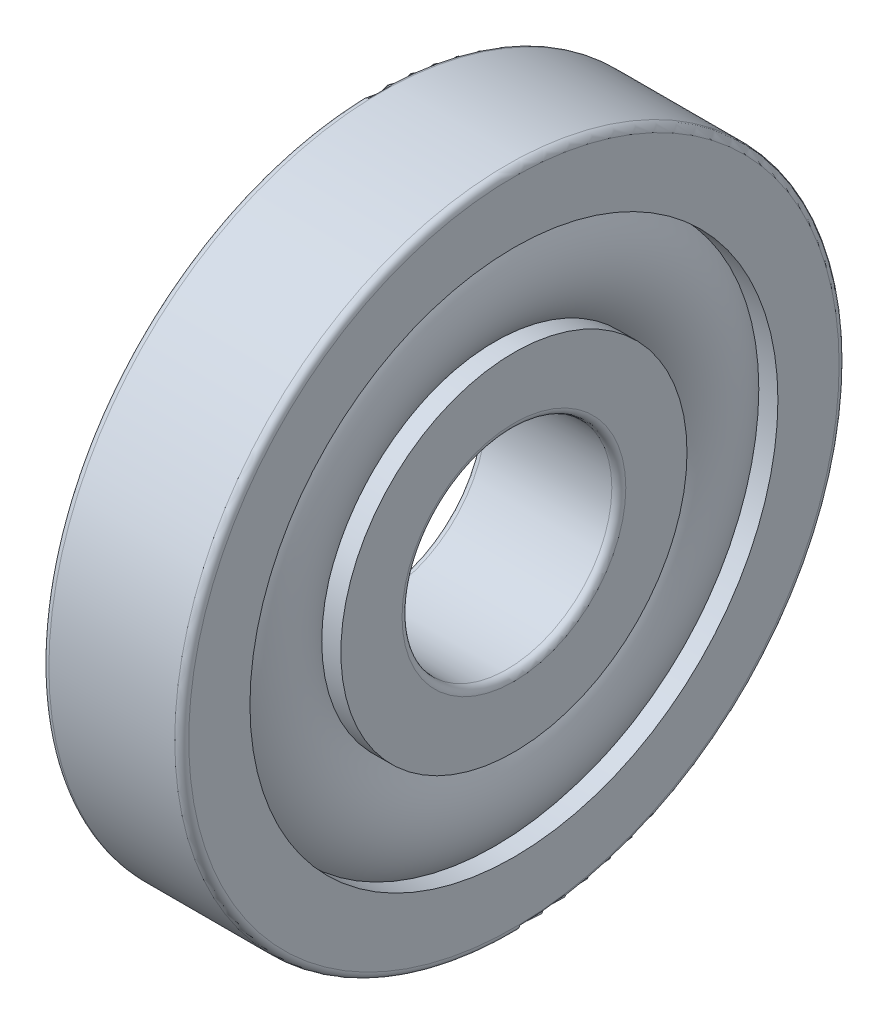
SolidWorks part; units mm, degrees
ref_plane "Plane1" through (0, 0, 0) normal (0, 0, 1) x (1, 0, 0)
ref_plane "Plane2" through (0, 0, 0) normal (0, 1, 0) x (1, 0, 0)
ref_plane "Plane3" through (0, 0, 0) normal (1, 0, 0) x (0, 0, -1)
sketch "Clipboard" plane through (0, 0, 0) normal (0, 0, 1) x (1, 0, 0)
  line L0 (-10, 0) -> (10, 0) construction
  line L1 (0, 0) -> (22.3471, -0.7804)
  line L2 (0, 0) -> (6.2462, 0.2181)
  line L3 (0, 0) -> (22.3471, -0.7804)
  line L4 (0, 0) -> (-22.3573, -0.3902)
  dimension "BallCLRad" = 6.25
sketch "CagSpiSke" plane through (0, 0, 0) normal (0, 0, 1) x (1, 0, 0)
  line L0 (0.195, 5.925) -> (0.195, 6.575)
  line L1 (0.195, 6.575) -> (-0.195, 6.575)
  line L2 (-0.195, 6.575) -> (-0.195, 5.925)
  line L3 (-0.195, 5.925) -> (0.195, 5.925)
  line L4 (-20.6375, 0) -> (20.6375, 0) construction
  line L5 (0, 0) -> (0, 23.7692) construction
  dimension "OD" = 13.15
  dimension "ID" = 11.85
revolve "CageSpine" add sketch "CagSpiSke" angle 0.001 about L4 reverse direction yes
ref_axis "Axis1" through (-50, 0, 0) along (1, 0, 0)
sketch "CagBalSke" plane through (0, 0, 0) normal (0, 0, 1) x (1, 0, 0)
  line L0 (-2.145, 6.25) -> (2.145, 6.25)
  line L1 (-1.905, 6.25) -> (1.905, 6.25) construction
  line L2 (-10, 0) -> (10, 0) construction
  line L3 (0, 0) -> (0, 24) construction
  arc A0 (2.145, 6.25) -> (-2.145, 6.25) centre (0, 6.25) cw
  dimension "BallCLRad" = 6.25
revolve "CageBall" [suppressed] add sketch "CagBalSke" angle 360 about L1 reverse direction yes
pattern_circular "CageBalls" [suppressed] count 2 every 180 about axis through (-50, 0, 0) along (1, 0, 0)
sketch "CagTrmODSke" plane through (0, 0, 0) normal (0, 0, 1) x (1, 0, 0)
  line L0 (2.146, 6.575) -> (2.146, 8.396)
  line L1 (2.146, 8.396) -> (-2.146, 8.396)
  line L2 (-2.146, 8.396) -> (-2.146, 6.575)
  line L3 (-2.146, 6.575) -> (2.146, 6.575)
  line L4 (-20.6375, 0) -> (20.6375, 0) construction
  line L5 (0, 0) -> (0, 25) construction
  dimension "Width" = 4.292
  dimension "ID" = 13.15
  dimension "OD" = 16.792
revolve "CageTrimOD" [suppressed] cut sketch "CagTrmODSke" angle 360 about L4 reverse direction yes
sketch "CagTrmIDSke" plane through (0, 0, 0) normal (0, 0, 1) x (1, 0, 0)
  line L0 (2.146, 4.106) -> (2.146, 5.925)
  line L1 (2.146, 5.925) -> (-2.146, 5.925)
  line L2 (-2.146, 5.925) -> (-2.146, 4.106)
  line L3 (-2.146, 4.106) -> (2.146, 4.106)
  line L4 (-20.6375, 0) -> (20.6375, 0) construction
  line L5 (0, 0) -> (0, 25) construction
  dimension "Width" = 4.292
  dimension "ID" = 8.212
  dimension "OD" = 11.85
revolve "CageTrimID" [suppressed] cut sketch "CagTrmIDSke" angle 360 about L4 reverse direction yes
sketch "BalSimSke" plane through (0, 0, 0) normal (0, 0, 1) x (1, 0, 0)
  line L0 (-10, 0) -> (10, 0) construction
  line L1 (-10, 6.25) -> (10, 6.25) construction
  line L2 (0, 0) -> (0, 23) construction
  circle A0 centre (0, 6.25) radius 1.95
  dimension "BallCLRad" = 6.25
  dimension "Ball_diameter" = 3.9
revolve "BallsSimplified" add sketch "BalSimSke" angle 360 about L0
sketch "BalDetSke" plane through (0, 0, 0) normal (0, 0, 1) x (1, 0, 0)
  line L0 (-1.95, 6.25) -> (1.95, 6.25)
  line L1 (-1.905, 6.25) -> (1.905, 6.25) construction
  line L2 (0, 0) -> (0, 25) construction
  arc A0 (1.95, 6.25) -> (-1.95, 6.25) centre (0, 6.25) cw
  dimension "BallCLRad" = 6.25
  dimension "Ball_diameter" = 3.9
revolve "BallDetailed" [suppressed] add sketch "BalDetSke" angle 360 about L1 reverse direction yes
sketch "InnRacSke" plane through (0, 0, 0) normal (0, 0, 1) x (1, 0, 0)
  line L0 (-1.4197, 4.95) -> (-2, 4.95)
  line L1 (-2, 4.95) -> (-2, 3.2)
  line L2 (-1.8, 3) -> (1.8, 3)
  line L3 (2, 3.2) -> (2, 4.95)
  line L4 (2, 4.95) -> (1.4197, 4.95)
  line L5 (-20.6375, 0) -> (20.6375, 0) construction
  line L6 (0, 0) -> (0, 30) construction
  arc A0 (-2, 3.2) -> (-1.8, 3) centre (-1.8, 3.2) ccw
  arc A1 (1.8, 3) -> (2, 3.2) centre (1.8, 3.2) ccw
  arc A2 (1.4197, 4.95) -> (-1.4197, 4.95) centre (0, 6.25) cw
  dimension "BallCLRad" = 6.25
  dimension "Fillet_radius" = 0.2
  dimension "Ball_diameter" = 3.85
  dimension "ID" = 6
  dimension "OD" = 9.9
  dimension "Width" = 4
revolve "InnerRace" add sketch "InnRacSke" angle 360 about L5 reverse direction yes
sketch "OutRacSke" plane through (0, 0, 0) normal (0, 0, 1) x (1, 0, 0)
  line L0 (-1.4197, 7.55) -> (-2, 7.55)
  line L1 (-2, 7.55) -> (-2, 9.3)
  line L2 (-1.8, 9.5) -> (1.8, 9.5)
  line L3 (2, 9.3) -> (2, 7.55)
  line L4 (2, 7.55) -> (1.4197, 7.55)
  line L5 (-20.6375, 0) -> (20.6375, 0) construction
  line L6 (0, 0) -> (0, 30) construction
  arc A0 (-2, 9.3) -> (-1.8, 9.5) centre (-1.8, 9.3) cw
  arc A1 (1.8, 9.5) -> (2, 9.3) centre (1.8, 9.3) cw
  arc A2 (1.4197, 7.55) -> (-1.4197, 7.55) centre (0, 6.25) ccw
  dimension "BallCLRad" = 6.25
  dimension "Fillet_radius" = 0.2
  dimension "Ball_diameter" = 3.85
  dimension "Width" = 4
revolve "OuterRace" add sketch "OutRacSke" angle 360 about L5 reverse direction yes
pattern_circular "BallsDetailed" [suppressed] count 2 every 180 about axis through (-50, 0, 0) along (1, 0, 0)
equation "\"BallCLRad@Clipboard\" = ( \"OD@OutRacSke\" + \"ID@InnRacSke\" ) / 4"
equation "\"BallCLRad@BalSimSke\" = \"BallCLRad@Clipboard\""
equation "\"BallCLRad@BalDetSke\" = \"BallCLRad@Clipboard\""
equation "\"BallCLRad@InnRacSke\" = \"BallCLRad@Clipboard\""
equation "\"BallCLRad@OutRacSke\" = \"BallCLRad@Clipboard\""
equation "\"Ball_diameter@InnRacSke\" = \"Ball_diameter@BalDetSke\" - 0.05"
equation "\"Ball_diameter@OutRacSke\" = \"Ball_diameter@BalDetSke\" - 0.05"
equation "\"Ball_diameter@BalSimSke\" = \"Ball_diameter@BalDetSke\""
equation "\"Width@OutRacSke\" = \"Width@InnRacSke\""
equation "\"Fillet_radius@OutRacSke\" = \"Fillet_radius@InnRacSke\""
equation "\"Max_count@Clipboard\" = int( 3.14159265 / atn(( \"Ball_diameter@BalDetSke\" / 2) / sqr( \"BallCLRad@Clipboard\"  *  \"BallCLRad@Clipboard\" - ( \"Ball_diameter@BalDetSke\" / 2) *  ( \"Ball_diameter@BalDetSke\" / 2))))"
equation "\"Max_count@Clipboard\" = ((sgn( \"Max_count@Clipboard\" - \"Count@Clipboard\" )-1)*( \"Max_count@Clipboard\" - \"Count@Clipboard\" ))/-2+ \"Count@Clipboard\""
equation "\"Count@BallsDetailed\" = int( \"Show_count@Clipboard\" ) "
equation "\"Count@BallsDetailed\" = ((sgn( \"Count@BallsDetailed\" - \"Max_count@Clipboard\" )-1)*( \"Count@BallsDetailed\" - \"Max_count@Clipboard\" ))/-2+ \"Max_count@Clipboard\""
equation "\"Count@BallsDetailed\" = ((sgn( \"Count@BallsDetailed\" - \"Min_count@Clipboard\" )+1)*( \"Count@BallsDetailed\" - \"Min_count@Clipboard\"))/2 +\"Min_count@Clipboard\""
equation "\"Angle@BallsDetailed\" = 360.0 / \"Max_count@Clipboard\""
equation "\"BallCLRad@CagBalSke\" = \"BallCLRad@Clipboard\""
equation "\"Count@CageBalls\" = \"Count@BallsDetailed\""
equation "\"Angle@CageBalls\" = \"Angle@BallsDetailed\""
equation "\"Angle@CageSpine\" =  \"Angle@CageBalls\" * ( \"Count@CageBalls\" -1 + int( \"Count@CageBalls\" / \"Max_count@Clipboard\" ) )  + 0.001 -  int( \"Count@CageBalls\" / \"Max_count@Clipboard\" ) * 0.001"
equation "\"Angle@CageSpine\" =  \"Angle@CageSpine\" * int( \"Min_count@Clipboard\" / 2) + int(1 / \"Min_count@Clipboard\")  * 0.001"
equation "\"CageWallOD@CagBalSke\" =  \"Ball_diameter@BalDetSke\" * 1.1"
equation "\"Thickness@CagSpiSke\" =  \"Ball_diameter@BalDetSke\" * 0.1"
equation "\"OD@CagTrmODSke\" = \"BallCLRad@Clipboard\" * 2 + \"CageWallOD@CagBalSke\" + 0.002"
equation "\"ID@CagTrmODSke\" = \"BallCLRad@Clipboard\" * 2 + \"Ball_diameter@BalDetSke\" / 6"
equation "\"OD@CagTrmIDSke\" = \"BallCLRad@Clipboard\" * 2 - \"Ball_diameter@BalDetSke\" / 6"
equation "\"ID@CagTrmIDSke\" = \"BallCLRad@Clipboard\" * 2 - \"CageWallOD@CagBalSke\" + 0.002"
equation "\"OD@CagSpiSke\" = \"ID@CagTrmODSke\""
equation "\"ID@CagSpiSke\" = \"OD@CagTrmIDSke\""
equation "\"Width@CagTrmODSke\" = \"CageWallOD@CagBalSke\" + 0.002"
equation "\"Width@CagTrmIDSke\" = \"CageWallOD@CagBalSke\" + 0.002"
